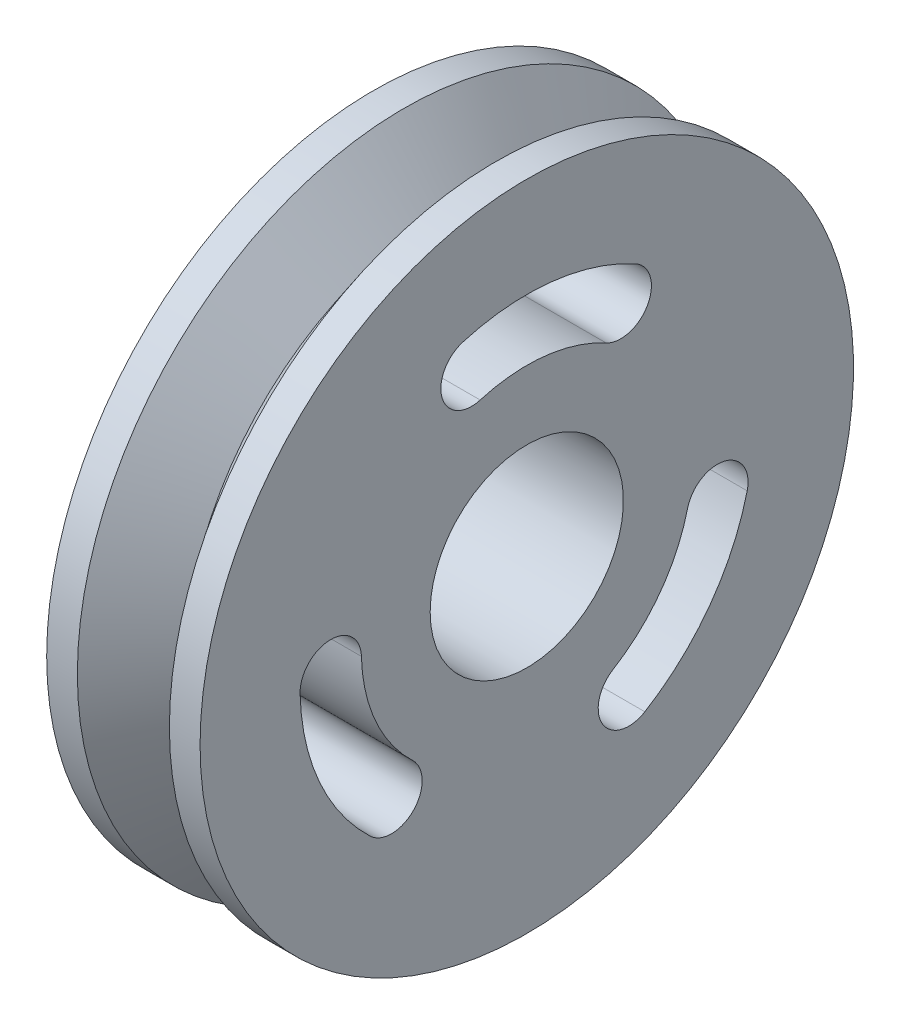
SolidWorks part; units mm, degrees
ref_plane "Front Plane" through (0, 0, 0) normal (0, 0, 1) x (1, 0, 0)
ref_plane "Top Plane" through (0, 0, 0) normal (0, 1, 0) x (1, 0, 0)
ref_plane "Right Plane" through (0, 0, 0) normal (1, 0, 0) x (0, 0, -1)
sketch "Sketch1" plane through (0, 0, 0) normal (0, 0, 1) x (1, 0, 0)
  line L0 (0, 0) -> (16.5774, 0) construction
  line L1 (1.27, 13.525) -> (3.175, 10.985)
  line L2 (0, 4) -> (6.35, 4)
  line L3 (0, 4) -> (0, 13.525)
  line L4 (0, 13.525) -> (1.27, 13.525)
  line L5 (6.35, 4) -> (6.35, 13.525)
  line L6 (3.175, 10.985) -> (5.08, 13.525)
  line L7 (3.175, 10.985) -> (3.175, 4) construction
  line L8 (5.08, 13.525) -> (6.35, 13.525)
  dimension "D1" = 8
  dimension "D2" = 9.525
  dimension "D3" = 6.35
  dimension "D4" = 1.27
  dimension "D5" = 2.54
revolve "Revolve1" add sketch "Sketch1" angle 360 about L0
sketch "Sketch2" plane through (0, 0, 0) normal (-1, 0, 0) x (0, 0, 1)
  arc A0 (1.93, 6.5699) -> (2.6459, 9.0069) centre (2.288, 7.7884) ccw construction
  arc A1 (1.93, 6.5699) -> (-3.2809, 6.0103) centre (0, 0) ccw construction
  arc A2 (-4.4979, 8.2398) -> (-3.2809, 6.0103) centre (-3.8894, 7.1251) ccw construction
  arc A3 (2.6459, 9.0069) -> (-4.4979, 8.2398) centre (0, 0) ccw construction
  arc A4 (1.93, 6.5699) -> (2.6459, 9.0069) centre (2.288, 7.7884) ccw
  arc A5 (1.93, 6.5699) -> (-3.2809, 6.0103) centre (0, 0) ccw
  arc A6 (-4.4979, 8.2398) -> (-3.2809, 6.0103) centre (-3.8894, 7.1251) ccw
  arc A7 (2.6459, 9.0069) -> (-4.4979, 8.2398) centre (0, 0) ccw
  arc A8 (4.7247, -4.9564) -> (6.4772, -6.7949) centre (5.601, -5.8756) ccw
  arc A9 (6.4772, -6.7949) -> (9.3848, -0.2246) centre (0, 0) ccw
  arc A10 (9.3848, -0.2246) -> (6.8455, -0.1638) centre (8.1152, -0.1942) ccw
  arc A11 (4.7247, -4.9564) -> (6.8455, -0.1638) centre (0, 0) ccw
  arc A12 (-6.6547, -1.6135) -> (-9.1232, -2.212) centre (-7.8889, -1.9128) ccw
  arc A13 (-9.1232, -2.212) -> (-4.8869, -8.0152) centre (0, 0) ccw
  arc A14 (-4.8869, -8.0152) -> (-3.5647, -5.8465) centre (-4.2258, -6.9308) ccw
  arc A15 (-6.6547, -1.6135) -> (-3.5647, -5.8465) centre (0, 0) ccw
  point P8 (0, 0)
  point P21 (0, 0)
  dimension "D1" = 3
extrude "Cut-Extrude1" cut sketch "Sketch2" against normal through all both and the other way through all
